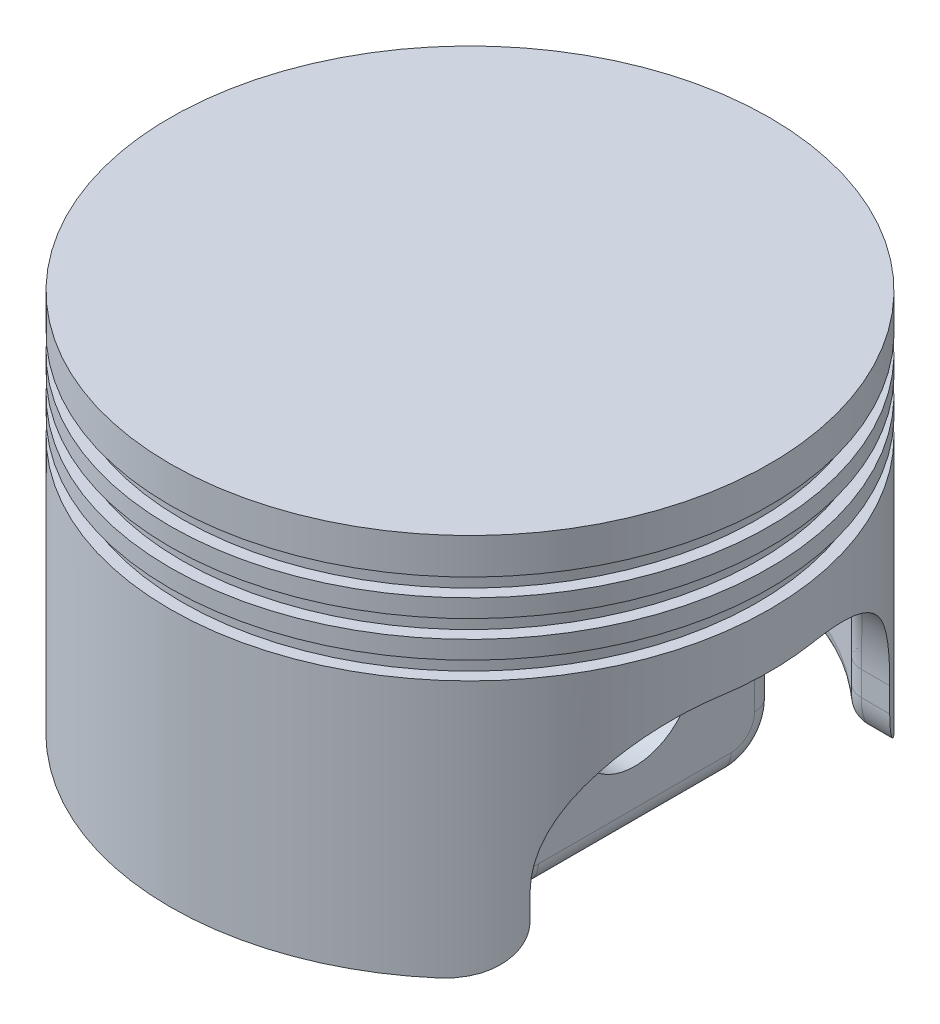
SolidWorks part; units mm, degrees
ref_plane "Front Plane" through (0, 0, 0) normal (0, 0, 1) x (1, 0, 0)
ref_plane "Top Plane" through (0, 0, 0) normal (0, 1, 0) x (1, 0, 0)
ref_plane "Right Plane" through (0, 0, 0) normal (1, 0, 0) x (0, 0, -1)
sketch "Sketch2" plane through (0, 0, 0) normal (0, 0, 1) x (1, 0, 0)
  line L0 (0, 0) -> (63.5, 0)
  line L1 (63.5, 0) -> (63.5, -81.28)
  line L2 (63.5, -81.28) -> (57.15, -81.28)
  line L3 (57.15, -81.28) -> (57.15, -19)
  line L4 (57.15, -19) -> (0, -19)
  line L5 (0, -19) -> (0, 0)
  dimension "D1" = 63.5
  dimension "D2" = 81.28
  dimension "D3" = 19
  dimension "D4" = 57.15
revolve "Revolve1" add sketch "Sketch2" angle 360 about L5
sketch "Sketch3" plane through (0, 0, 0) normal (1, 0, 0) x (0, 0, -1)
  line L0 (-63.5, -81.28) -> (63.5, -81.28) construction
  line L1 (-38.1, -38.1) -> (38.1, -38.1)
  line L2 (-38.1, -38.1) -> (-38.1, -81.28)
  line L3 (-38.1, -81.28) -> (38.1, -81.28)
  line L4 (38.1, -38.1) -> (38.1, -81.28)
  line L5 (-38.1, -38.1) -> (38.1, -81.28) construction
  line L6 (-38.1, -81.28) -> (38.1, -38.1) construction
  point P0 (0, -59.69)
  dimension "D1" = 76.2
  dimension "D2" = 43.18
extrude "Cut-Extrude1" cut sketch "Sketch3" against normal through all both and the other way through all
sketch "Sketch4" plane through (0, 0, 0) normal (1, 0, 0) x (0, 0, -1)
  line L0 (0, 0) -> (0, -26.7134) construction
  line L1 (63.5, -81.28) -> (63.5, 0) construction
  line L2 (60.96, -7.62) -> (66.04, -7.62)
  line L3 (60.96, -7.62) -> (60.96, -11.43)
  line L4 (60.96, -11.43) -> (66.04, -11.43)
  line L5 (66.04, -7.62) -> (66.04, -11.43)
  line L6 (60.96, -7.62) -> (66.04, -11.43) construction
  line L7 (60.96, -11.43) -> (66.04, -7.62) construction
  line L8 (63.5, 0) -> (-63.5, 0) construction
  point P3 (63.5, -9.525)
  dimension "D1" = 3.81
  dimension "D2" = 2.54
  dimension "D3" = 7.62
revolve "Cut-Revolve1" cut sketch "Sketch4" angle 360 about L0
pattern_linear "LPattern1" count 3 spacing 7.62 along (0, -1, 0) of "Cut-Revolve1"
sketch "Sketch5" plane through (0, -19, 0) normal (0, -1, 0) x (1, 0, 0)
  line L0 (0, 0) -> (0, 37.2109) construction
  line L1 (34.88, 30.4) -> (15.88, 30.4)
  line L2 (-34.88, -30.4) -> (-15.88, -30.4)
  line L3 (-34.88, -30.4) -> (-34.88, 30.4)
  line L4 (-34.88, 30.4) -> (-15.88, 30.4)
  line L5 (-15.88, -30.4) -> (-15.88, 30.4)
  line L6 (-34.88, -30.4) -> (-15.88, 30.4) construction
  line L7 (-34.88, 30.4) -> (-15.88, -30.4) construction
  line L8 (15.88, -30.4) -> (15.88, 30.4)
  line L9 (34.88, -30.4) -> (15.88, -30.4)
  line L10 (34.88, -30.4) -> (34.88, 30.4)
  point P3 (-25.38, 0)
  dimension "D1" = 19
  dimension "D2" = 60.8
  dimension "D3" = 31.76
  dimension "D4" = 15.88
extrude "Boss-Extrude1" add sketch "Sketch5" along normal blind 63.5
sketch "Sketch6" plane through (-34.88, 0, 0) normal (-1, 0, 0) x (0, 0, 1)
  line L0 (30.4, -82.5) -> (-30.4, -82.5) construction
  circle A0 centre (0, -57.1) radius 12.7
  dimension "D1" = 25.4
  dimension "D2" = 25.4
extrude "Cut-Extrude2" cut sketch "Sketch6" against normal through all both and the other way through all
fillet "Fillet1" radius 28 4 edges at (46.6985, -38.1, 38.1) (46.6985, -38.1, -38.1) (-46.6985, -38.1, -38.1) (-46.6985, -38.1, 38.1)
fillet "Fillet2" radius 10 4 edges at (-25.38, -82.5, 30.4) (25.38, -82.5, 30.4) (-25.38, -82.5, -30.4) (25.38, -82.5, -30.4)
fillet "Fillet3" radius 10 4 edges at (-46.6985, -81.28, 38.1) (-46.6985, -81.28, -38.1) (46.6985, -81.28, -38.1) (46.6985, -81.28, 38.1)
fillet "Fillet4" radius 5 36 edges at (34.88, -79.5711, -27.4711) (15.88, -79.5711, -27.4711) (15.88, -45.75, -30.4) (15.88, -45.75, 30.4) (15.88, -79.5711, 27.4711) (15.88, -82.5, 0) (34.88, -45.75, 30.4) (34.88, -79.5711, 27.4711) (34.88, -82.5, 0) (34.88, -45.75, -30.4) (-15.88, -79.5711, 27.4711) (-15.88, -45.75, 30.4) (-15.88, -82.5, 0) (-15.88, -79.5711, -27.4711) (-15.88, -45.75, -30.4) (-34.88, -79.5711, 27.4711) (-34.88, -45.75, 30.4) (-34.88, -45.75, -30.4) (-34.88, -79.5711, -27.4711) (-34.88, -82.5, 0) (41.3657, -76.2692, 39.4335) (42.5971, -68.69, 38.1) (50.4318, -43.6881, 26.8841) (57.15, -38.1, 0) (46.055, -51.2516, -33.8387) (42.5971, -68.69, -38.1) (40.0022, -78.1316, -40.816) (-41.3657, -76.2692, -39.4335) (-42.5971, -68.69, -38.1) (-50.4318, -43.6881, -26.8841) (-57.15, -38.1, 0) (-46.055, -51.2516, 33.8387) (-42.5971, -68.69, 38.1) (-40.0022, -78.1316, 40.816) (0, -81.28, 57.15) (0, -81.28, -57.15)
fillet "Fillet5" radius 5 16 edges at (-17.3445, -19, 28.9355) (-25.38, -19, 30.4) (-33.4155, -19, 28.9355) (-33.4155, -19, -28.9355) (-25.38, -19, -30.4) (-17.3445, -19, -28.9355) (-15.88, -19, 0) (-34.88, -19, 0) (33.4155, -19, 28.9355) (25.38, -19, 30.4) (17.3445, -19, 28.9355) (17.3445, -19, -28.9355) (25.38, -19, -30.4) (33.4155, -19, -28.9355) (34.88, -19, 0) (15.88, -19, 0)
